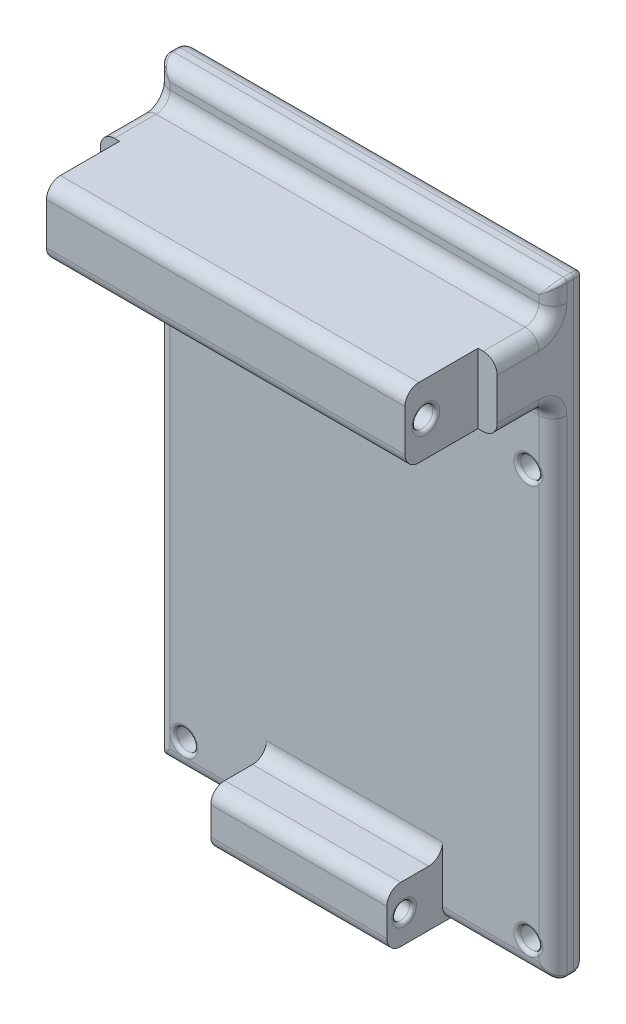
SolidWorks part; units mm, degrees
ref_plane "Plan de face" through (0, 0, 0) normal (0, 0, 1) x (1, 0, 0)
ref_plane "Plan de dessus" through (0, 0, 0) normal (0, 1, 0) x (1, 0, 0)
ref_plane "Plan de droite" through (0, 0, 0) normal (1, 0, 0) x (0, 0, -1)
sketch "Esquisse1" plane through (0, 0, 0) normal (0, 0, 1) x (1, 0, 0)
  line L0 (4, 4) -> (53.4, 4) construction
  line L1 (0, 0) -> (57, 0)
  line L2 (0, 0) -> (0, 87)
  line L3 (0, 87) -> (57, 87)
  line L4 (57, 0) -> (57, 87)
  line L5 (53.4, 4) -> (53.4, 62.6) construction
  line L6 (53.4, 62.6) -> (4, 62.6) construction
  circle A0 centre (4, 4) radius 1.5
  circle A1 centre (53.4, 4) radius 1.5
  circle A2 centre (53.4, 62.6) radius 1.5
  circle A3 centre (4, 62.6) radius 1.5
  dimension "D5" = 3
  dimension "D1" = 57
  dimension "D2" = 87
  dimension "D3" = 4
  dimension "D4" = 4
  dimension "D6" = 49.4
  dimension "D7" = 58.6
extrude "Boss.-Extru.1" add sketch "Esquisse1" along normal blind 5
sketch "Esquisse2" plane through (0, 0, 5) normal (0, 0, 1) x (1, 0, 0)
  line L0 (0, 0) -> (57, 0) construction
  line L1 (15.85, 0) -> (41.15, 0)
  line L2 (15.85, 0) -> (15.85, 8)
  line L3 (15.85, 8) -> (41.15, 8)
  line L4 (41.15, 0) -> (41.15, 8)
  line L5 (15.85, 0) -> (0, 0) construction
  line L6 (41.15, 0) -> (57, 0) construction
  dimension "D1" = 25.3
  dimension "D2" = 8
extrude "Boss.-Extru.2" add sketch "Esquisse2" along normal blind 8
sketch "Esquisse3" plane through (15.85, 0, 0) normal (-1, 0, 0) x (0, 0, 1)
  line L0 (13, 4) -> (10.5, 4) construction
  line L1 (13, 8) -> (13, 0) construction
  circle A0 centre (10.5, 4) radius 1.25
  dimension "D2" = 2.5
  dimension "D1" = 2.5
extrude "Enlèv. mat.-Extru.1" cut sketch "Esquisse3" against normal through all
sketch "Esquisse4" plane through (0, 0, 5) normal (0, 0, 1) x (1, 0, 0)
  line L5 (0, 87) -> (0, 0) construction
  line L6 (0, 82) -> (57, 82)
  line L7 (0, 82) -> (0, 72)
  line L8 (0, 72) -> (57, 72)
  line L9 (57, 82) -> (57, 72)
  line L10 (57, 0) -> (57, 87) construction
  line L11 (57, 87) -> (0, 87) construction
  dimension "D1" = 10
  dimension "D2" = 5
extrude "Boss.-Extru.3" add sketch "Esquisse4" along normal blind 8
sketch "Esquisse5" plane through (0, 0, 13) normal (0, 0, 1) x (1, 0, 0)
  line L6 (57, 82) -> (0, 82) construction
  line L7 (2.75, 82) -> (54.25, 82)
  line L12 (2.75, 82) -> (2.75, 72)
  line L13 (2.75, 72) -> (54.25, 72)
  line L14 (54.25, 82) -> (54.25, 72)
  line L15 (0, 72) -> (57, 72) construction
  line L16 (0, 82) -> (2.75, 82) construction
  line L17 (54.25, 82) -> (57, 82) construction
  dimension "D1" = 51.5
extrude "Boss.-Extru.4" add sketch "Esquisse5" along normal blind 10.5
sketch "Esquisse6" plane through (2.75, 0, 0) normal (-1, 0, 0) x (0, 0, 1)
  line L0 (20.5, 82) -> (20.5, 72) construction
  line L3 (23.5, 82) -> (13, 82) construction
  line L5 (23.5, 72) -> (13, 72) construction
  line L6 (23.5, 82) -> (23.5, 72) construction
  circle A3 centre (20.5, 77) radius 1.5
  dimension "D2" = 3
  dimension "D1" = 3
extrude "Enlèv. mat.-Extru.2" cut sketch "Esquisse6" against normal through all
fillet "Congé1" radius 2 22 edges at (28.5, 8, 5) (28.5, 0, 13) (28.5, 8, 13) (28.5, 82, 23.5) (57, 84.5, 5) (0, 84.5, 5) (0, 72, 9) (57, 72, 9) (57, 82, 9) (0, 82, 9) (28.5, 72, 5) (28.5, 82, 5) (57, 43.5, 0) (0, 43.5, 0) (57, 36, 5) (0, 36, 5) (49.075, 0, 5) (7.925, 0, 5) (28.5, 0, 0) (28.5, 87, 0) (28.5, 87, 5) (28.5, 72, 23.5)
fillet "Congé2" radius 0.5 24 edges at (5.5, 62.6, 0) (5.5, 4, 0) (54.9, 4, 0) (54.9, 62.6, 0) (15.85, 4, 11.75) (41.15, 2.75, 10.5) (54.9, 62.6, 5) (5.5, 62.6, 5) (5.5, 4, 5) (54.9, 4, 5) (57, 87, 2.5) (0, 87, 2.5) (0, 0, 2.5) (57, 0, 2.5) (56.4142, 86.4142, 4.4142) (56.4142, 86.4142, 0.5858) (0.5858, 86.4142, 4.4142) (0.5858, 86.4142, 0.5858) (0.5858, 0.5858, 4.4142) (0.5858, 0.5858, 0.5858) (56.4142, 0.5858, 4.4142) (56.4142, 0.5858, 0.5858) (54.25, 75.5, 20.5) (2.75, 77, 22)
